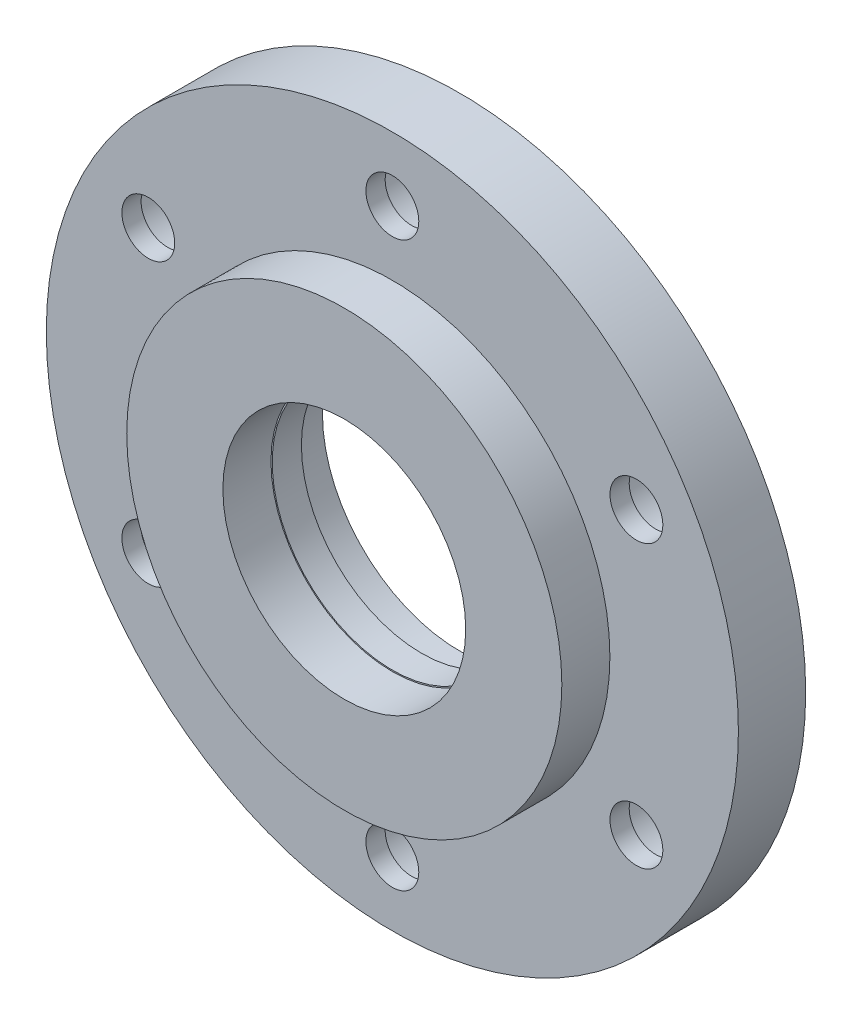
SolidWorks part; units mm, degrees
material "6061-T6 (SS)"
ref_plane "Front Plane" through (0, 0, 0) normal (0, 0, 1) x (1, 0, 0)
ref_plane "Top Plane" through (0, 0, 0) normal (0, 1, 0) x (1, 0, 0)
ref_plane "Right Plane" through (0, 0, 0) normal (1, 0, 0) x (0, 0, -1)
sketch "Sketch Spindle Skeleton" plane through (0, 0, 0) normal (1, 0, 0) x (0, 0, -1)
  line L0 (-114.9, -9.5) -> (-144, -9.5)
  line L5 (-1000, 0) -> (49000, 0)
  line L6 (0, -9.5) -> (0, 9.5)
  line L13 (0, 9.5) -> (-53.3, 9.5)
  line L26 (-53.3, 9.5) -> (-53.3, 14)
  line L27 (-53.3, 14) -> (-114.9, 14)
  line L32 (-114.9, 14) -> (-114.9, 9.5)
  line L34 (-160, 7) -> (-160, -7)
  line L36 (-114.9, -9.5) -> (-114.9, -14)
  line L37 (-114.9, -14) -> (-53.3, -14)
  line L38 (-53.3, -14) -> (-53.3, -9.5)
  line L39 (0, -9.5) -> (-53.3, -9.5)
  line L40 (-21.7, 36) -> (-14.7, 36)
  line L41 (-131.5, 22.6312) -> (-114.9, 22.6312)
  line L42 (-131.5, 22.6312) -> (-131.5, -22.6312)
  line L43 (-131.5, -22.6312) -> (-114.9, -22.6312)
  line L44 (-114.9, 22.6312) -> (-114.9, -22.6312)
  line L45 (-131.5, 22.6312) -> (-114.9, -22.6312) construction
  line L46 (-131.5, -22.6312) -> (-114.9, 22.6312) construction
  line L47 (-36.7, 22.6312) -> (-53.3, 22.6312)
  line L48 (-36.7, 22.6312) -> (-36.7, -22.6312)
  line L49 (-36.7, -22.6312) -> (-53.3, -22.6312)
  line L50 (-53.3, 22.6312) -> (-53.3, -22.6312)
  line L51 (-36.7, 22.6312) -> (-53.3, -22.6312) construction
  line L52 (-36.7, -22.6312) -> (-53.3, 22.6312) construction
  line L59 (-14.7, 36) -> (-14.7, -36)
  line L60 (-14.7, -36) -> (-21.7, -36)
  line L61 (-21.7, -22.6312) -> (-26.7, -22.6312)
  line L62 (-26.7, -22.6312) -> (-26.7, -12.6312)
  line L63 (-26.7, -12.6312) -> (-21.7, -12.6312)
  line L64 (-21.7, -12.6312) -> (-21.7, 12.6312)
  line L65 (-21.7, 12.6312) -> (-26.7, 12.6312)
  line L66 (-26.7, 12.6312) -> (-26.7, 22.6312)
  line L67 (-26.7, 22.6312) -> (-21.7, 22.6312)
  line L68 (-21.7, 22.6312) -> (-21.7, 36)
  line L69 (-21.7, -22.6312) -> (-21.7, -36)
  line L71 (-133.659, 36) -> (-22.7, 36)
  line L72 (-133.659, 36) -> (-133.659, -36)
  line L73 (-133.659, -36) -> (-22.7, -36)
  line L74 (-22.7, 36) -> (-22.7, -36)
  line L75 (-133.659, 36) -> (-22.7, -36) construction
  line L76 (-133.659, -36) -> (-22.7, 36) construction
  line L77 (-144, -9.5) -> (-144, -7)
  line L78 (-144, -7) -> (-160, -7)
  line L79 (-114.9, 9.5) -> (-144, 9.5)
  line L80 (-144, 7) -> (-160, 7)
  line L81 (-144, 9.5) -> (-144, 7)
  line L82 (-129.45, 9.5) -> (-129.45, -9.5) construction
  line L83 (-26.65, 9.5) -> (-26.65, -9.5) construction
  line L96 (-133.659, 36) -> (-140.659, 36)
  line L98 (-133.659, -36) -> (-140.659, -36)
  line L99 (-140.659, 36) -> (-140.659, -36)
  line L110 (-133.659, 36) -> (-133.659, -36)
  point P3 (0, 0)
  point P18 (-123.2, 0)
  point P24 (-45, 0)
  point P29 (-78.1795, 0)
  point P48 (-14.7, 29.3156)
  point P58 (0, 0)
  point P70 (-140.659, 29.3156)
revolve "Main Revolve" add sketch "Sketch Spindle Skeleton" angle 360 about L5 region at (0, 22.4882, 18.4046) region at (0, 17.6312, 24.7)
sketch "Sketch Center Cut" plane through (0, 0, 21.7) normal (0, 0, 1) x (1, 0, 0)
  circle A0 centre (0, 0) radius 12.6312 construction
  circle A1 centre (0, 0) radius 12.6312 construction
  circle A2 centre (0, 0) radius 12.5
  dimension "D1" = 25
extrude "Cut Center" cut sketch "Sketch Center Cut" against normal through all
hole_wizard "CBORE for M5 SHCS2" positions "Hole wizard sketch 1" profile "Hole wizard sketch 2" counterbore size "M5" standard "ANSI Metric" end condition through all
sketch "Hole wizard sketch 1" plane through (0, 0, 14.7) normal (0, 0, -1) x (-1, 0, 0)
  point P0 (0, 29.3156)
sketch "Hole wizard sketch 2" plane through (0, 29.3156, 14.7) normal (1, 0, 0) x (0, 1, 0)
  line L0 (0, 0) -> (0, 12)
  line L1 (0, 12) -> (2.75, 12)
  line L3 (2.75, 12) -> (2.75, 5)
  line L4 (2.75, 5) -> (5, 5)
  line L5 (5, 5) -> (5, 0)
  line L7 (5, 0) -> (0, 0)
  line L11 (0, -6.35) -> (0, 107.95) construction
  dimension "Thru Hole Dia." = 5.5
  dimension "Thru Hole Depth" = 12
  dimension "C'Bore Dia." = 10
  dimension "C'Bore Depth" = 5
pattern_circular "CirPattern1" count 6 over 360 about axis through (0, 0, 14.7) along (0, 0, 1) of "CBORE for M5 SHCS2"
sketch "Sketch1" plane through (0, 0, 14.7) normal (0, 0, -1) x (-1, 0, 0)
  circle A0 centre (0, 0) radius 14.2748
  dimension "D1" = 28.5496
extrude "Cut-Extrude1" cut sketch "Sketch1" against normal blind 3.9624
